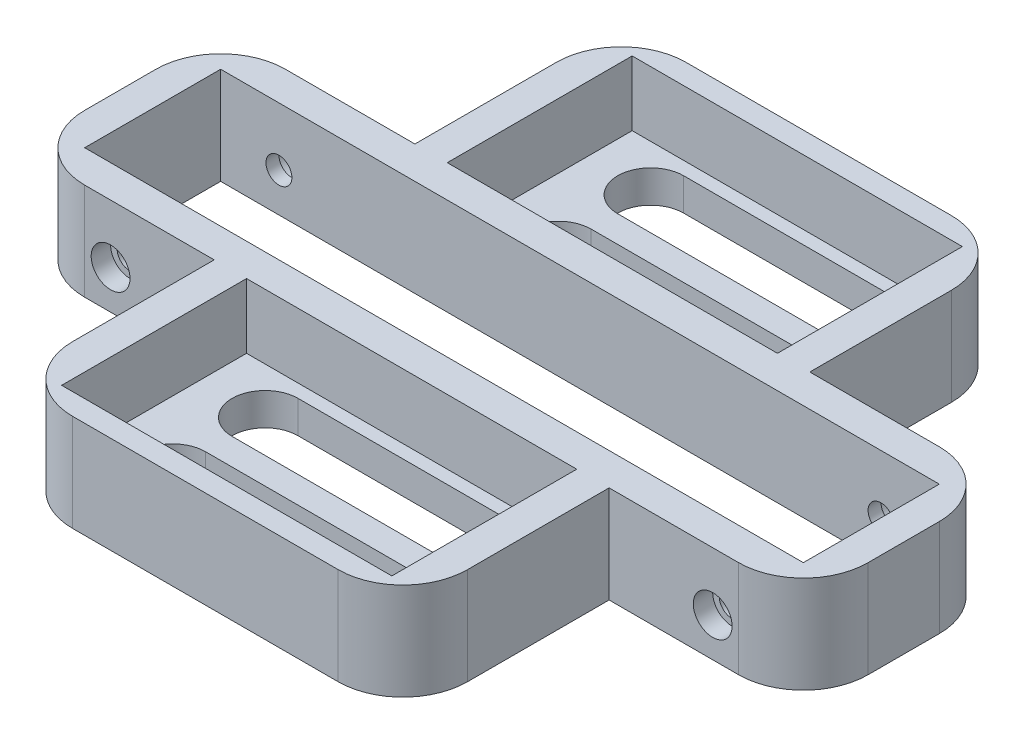
SolidWorks part; units mm, degrees
other "Markup1"
sketch "Sketch4" plane through (-60.5, 10, 46.36) normal (-0.2171, 0.8708, 0.4411) x (0.5241, -0.2773, 0.8053)
ref_plane "Front Plane" through (0, 0, 0) normal (0, 0, 1) x (1, 0, 0)
ref_plane "Top Plane" through (0, 0, 0) normal (0, 1, 0) x (1, 0, 0)
ref_plane "Right Plane" through (0, 0, 0) normal (1, 0, 0) x (0, 0, -1)
sketch "Sketch1" plane through (0, 0, 0) normal (0, 1, 0) x (1, 0, 0)
  line L0 (0, 47.36) -> (0, -47.36) construction
  line L1 (-30.5, -47.36) -> (30.5, -47.36)
  line L2 (-30.5, -47.36) -> (-30.5, -15.5)
  line L3 (-30.5, 47.36) -> (30.5, 47.36)
  line L4 (30.5, -47.36) -> (30.5, -15.5)
  line L5 (-30.5, -47.36) -> (30.5, 47.36) construction
  line L6 (-30.5, 47.36) -> (30.5, -47.36) construction
  line L11 (-30.5, -15.5) -> (30.5, 15.5) construction
  line L12 (-30.5, 15.5) -> (30.5, -15.5) construction
  line L13 (30.5, 15.5) -> (60.5, 15.5)
  line L15 (30.5, -15.5) -> (60.5, -15.5)
  line L16 (60.5, 15.5) -> (60.5, -15.5)
  line L22 (30.5, 15.5) -> (-30.5, 15.5)
  line L23 (-30.5, -15.5) -> (30.5, -15.5)
  line L24 (-30.5, -15.5) -> (-60.5, -15.5)
  line L25 (-60.5, 15.5) -> (-60.5, -15.5)
  line L26 (-30.5, 15.5) -> (-60.5, 15.5)
  line L28 (-30.5, 15.5) -> (-30.5, 47.36)
  line L29 (30.5, 15.5) -> (30.5, 47.36)
  line L30 (-30.5, 10.5) -> (-55.5, 10.5)
  line L31 (-55.5, 10.5) -> (-55.5, -10.5)
  line L32 (-30.5, -10.5) -> (-55.5, -10.5)
  line L33 (-30.5, -10.5) -> (30.5, -10.5)
  line L34 (30.5, -10.5) -> (55.5, -10.5)
  line L35 (55.5, 10.5) -> (55.5, -10.5)
  line L36 (30.5, 10.5) -> (55.5, 10.5)
  line L37 (30.5, 10.5) -> (-30.5, 10.5)
  line L38 (-60.5, 0) -> (60.5, 0) construction
  line L39 (-25.5, 44.06) -> (25.5, 44.06)
  line L40 (-25.5, 44.06) -> (-25.5, 15.5)
  line L41 (-25.5, 15.5) -> (25.5, 15.5)
  line L42 (25.5, 44.06) -> (25.5, 15.5)
  line L43 (-25.5, -15.5) -> (25.5, -15.5)
  line L44 (25.5, -44.06) -> (25.5, -15.5)
  line L45 (-25.5, -44.06) -> (25.5, -44.06)
  line L46 (-25.5, -44.06) -> (-25.5, -15.5)
  line L47 (-15.5, 36.92) -> (15.5, 36.92) construction
  line L48 (-15.5, 42.01) -> (15.5, 42.01)
  line L49 (-15.5, 31.83) -> (15.5, 31.83)
  line L50 (-25.5, 29.78) -> (25.5, 29.78) construction
  line L51 (-15.5, 22.64) -> (15.5, 22.64) construction
  line L52 (-15.5, 17.55) -> (15.5, 17.55)
  line L53 (-15.5, 27.73) -> (15.5, 27.73)
  line L54 (-15.5, -22.64) -> (15.5, -22.64) construction
  line L55 (-15.5, -17.55) -> (15.5, -17.55)
  line L56 (-15.5, -27.73) -> (15.5, -27.73)
  line L57 (-15.5, -36.92) -> (15.5, -36.92) construction
  line L58 (-15.5, -42.01) -> (15.5, -42.01)
  line L59 (-15.5, -31.83) -> (15.5, -31.83)
  arc A0 (-15.5, 42.01) -> (-15.5, 31.83) centre (-15.5, 36.92) ccw
  arc A1 (15.5, 31.83) -> (15.5, 42.01) centre (15.5, 36.92) ccw
  arc A2 (-15.5, 17.55) -> (-15.5, 27.73) centre (-15.5, 22.64) cw
  arc A3 (15.5, 27.73) -> (15.5, 17.55) centre (15.5, 22.64) cw
  arc A4 (-15.5, -17.55) -> (-15.5, -27.73) centre (-15.5, -22.64) ccw
  arc A5 (15.5, -27.73) -> (15.5, -17.55) centre (15.5, -22.64) ccw
  arc A6 (-15.5, -42.01) -> (-15.5, -31.83) centre (-15.5, -36.92) cw
  arc A7 (15.5, -31.83) -> (15.5, -42.01) centre (15.5, -36.92) cw
  point P0 (0, 0)
  point P5 (0, 0)
  point P29 (0, 44.06)
  point P38 (0, 36.92)
  point P43 (0, 0)
  point P44 (0, 39.2693)
  point P47 (0, 37.4502)
  point P50 (0, 22.64)
  point P57 (0, -22.64)
  point P64 (0, -36.92)
  dimension "D1" = 61
  dimension "D4" = 30
  dimension "D2" = 31.86
  dimension "D3" = 31
  dimension "D6" = 51
  dimension "D7" = 28.56
  dimension "D8" = 10.18
  dimension "D10" = 31
  dimension "D9" = 7.14
  dimension "D5" = 5
extrude "Boss-Extrude1" add sketch "Sketch1" along normal blind 10 contours L39 L42 L22 L29 L3 L28 L40 | L22 L26 L25 L24 L23 L15 L16 L13 L37 L36 L35 L34 L33 L32 L31 L30 | L45 L46 L23 L2 L1 L4 L44 region at (-29.8118, 0, 31.43) region at (-45.5, 0, 14.2509) region at (-29.8118, 0, -31.43)
extrude "Boss-Extrude2" add sketch "Sketch1<3>" against normal blind 5 contours L45 L46 L23 L2 L1 L4 L44 | L46 L45 L44 L23 | L22 L26 L25 L24 L23 L15 L16 L13 L37 L36 L35 L34 L33 L32 L31 L30 | L39 L42 L22 L29 L3 L28 L40 | L42 L39 L40 L22 region at (-29.8118, 0, 31.43) region at (-45.5, 0, 14.2509) region at (0, 0, 29.78) region at (-29.8118, 0, -31.43) region at (0, 0, -29.78)
sketch "Sketch1<3>" plane through (0, 0, 0) normal (0, 1, 0) x (1, 0, 0) same geometry as "Sketch1"
sketch "Sketch3" plane through (0, 0, 0) normal (0, 0, 1) x (1, 0, 0)
  line L0 (0, 10) -> (0, -5) construction
  line L1 (-60.5, 10) -> (-30.5, 10)
  line L2 (-60.5, 10) -> (-60.5, -5)
  line L3 (-60.5, -5) -> (-30.5, -5)
  line L4 (-30.5, 10) -> (-30.5, -5)
  line L5 (-30.5, 10) -> (30.5, 10) construction
  line L6 (0, -55) -> (0, 55) construction
  line L7 (-30.5, -5) -> (30.5, -5) construction
  circle A0 centre (-46.5, 1) radius 3
  circle A1 centre (-46.5, 1) radius 2
  circle A2 centre (46.5, 1) radius 2
  circle A3 centre (46.5, 1) radius 3
  dimension "D3" = 6
  dimension "D4" = 4
  dimension "D1" = 16
  dimension "D2" = 6
extrude "Cut-Extrude1" cut sketch "Sketch3" against normal up to surface and the other way up to surface contours A1 | A0 A1 | A2 | A3 A2 region at (-49.4151, 1, 0) region at (-46.5, 1, 0) region at (46.5, 1, 0) region at (43.5849, 1, 0) up to face at (-45.5, 2.5, -15.5) other way up to face at (-45.5, 2.5, 15.5)
extrude "Boss-Extrude3" add sketch "Sketch3<5>" along normal blind 12.5 and the other way blind 12.5 contours A0 A1 | A3 A2 region at (-49.4151, 1, 0) region at (43.5849, 1, 0)
sketch "Sketch3<5>" plane through (0, 0, 0) normal (0, 0, 1) x (1, 0, 0) same geometry as "Sketch3"
extrude "Cut-Extrude5" cut sketch "Sketch3<12>" against normal blind 10.5 and the other way up to surface (10.5 mm away) contours A3 A2 | A0 A1 region at (-49.4151, 1, 0) region at (43.5849, 1, 0) other way up to face at (43.5, 1, 10.5)
sketch "Sketch3<12>" plane through (0, 0, 0) normal (0, 0, 1) x (1, 0, 0) same geometry as "Sketch3"
fillet "Fillet1" radius 10 8 edges at (30.5, 2.5, -47.36) (60.5, 2.5, -15.5) (60.5, 2.5, 15.5) (30.5, 2.5, 47.36) (-30.5, 2.5, -47.36) (-60.5, 2.5, -15.5) (-30.5, 2.5, 47.36) (-60.5, 2.5, 15.5)
equation "\"W_d\"= 15mm"
equation "\"F\"= 17.5"
equation "\"A\"= 31mm"
equation "\"G\"= 18.15mm"
equation "\"W_t\"= 5mm"
equation "\"B\"= 51mm"
equation "\"E\"= 14.18mm"
equation "\"D1@Sketch1\"= \"B\" + 2 * \"W_t\""
equation "\"D4@Sketch1\"= \"W_d\" + 15"
equation "\"D2@Sketch1\" = \"E\" * 2 + 3.5mm"
equation "\"D3@Sketch1\"= \"A\""
equation "\"D6@Sketch1\"= \"B\""
equation "\"D7@Sketch1\" = 2 * \"E\" + 0.2mm"
equation "\"B_d1\"= 4mm"
equation "\"B_d2\"= 6mm"
equation "\"S1\"= 16mm"
equation "\"S2\"= 6mm"
equation "\"D2@Sketch3\"= \"S2\""
equation "\"D1@Sketch3\"= \"S1\""
equation "\"D4@Sketch3\"= \"B_d1\""
equation "\"D3@Sketch3\"= \"B_d2\""
equation "\"D8@Sketch1\"= \"E\" - 4mm"
equation "\"D10@Sketch1\" = \"B\" - 20mm"
equation "\"D9@Sketch1\"= ( 2 * \"E\" + 0.2 ) / 4"
